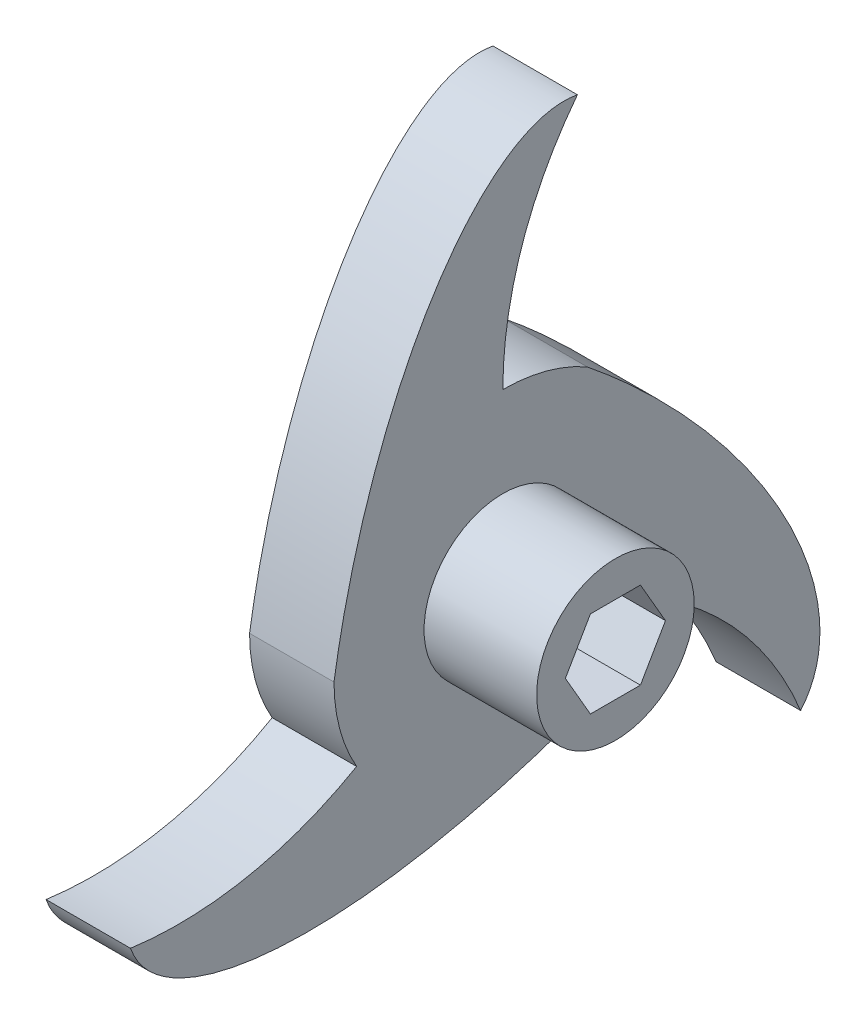
SolidWorks part; units mm, degrees
material "ABS"
ref_plane "Front Plane" through (0, 0, 0) normal (0, 0, 1) x (1, 0, 0)
ref_plane "Top Plane" through (0, 0, 0) normal (0, 1, 0) x (1, 0, 0)
ref_plane "Right Plane" through (0, 0, 0) normal (1, 0, 0) x (0, 0, -1)
sketch "Sketch1" plane through (0, 0, 0) normal (1, 0, 0) x (0, 0, -1)
  line L0 (0, 19.05) -> (101.4565, 19.05) construction
  line L1 (0, 0) -> (0, -44.45) construction
  line L2 (55, 0) -> (-55, 0) construction
  line L3 (0, 0) -> (-44.45, 0) construction
  line L5 (5.6459, 0) -> (2.823, 4.8895)
  line L6 (2.823, 4.8895) -> (-2.823, 4.8895)
  line L7 (-2.823, 4.8895) -> (-5.6459, 0)
  line L8 (-5.6459, 0) -> (-2.823, -4.8895)
  line L9 (-2.823, -4.8895) -> (2.823, -4.8895)
  line L10 (2.823, -4.8895) -> (5.6459, 0)
  circle A0 centre (0, 0) radius 19.05
  circle A1 centre (0, 0) radius 44.45
  arc A2 (0, 19.05) -> (8.4133, 43.6465) centre (40.1609, 19.05) cw
  arc A3 (16.4978, -9.525) -> (33.5923, -29.1094) centre (-3.5827, -44.3054) cw
  arc A4 (-16.4978, -9.525) -> (-42.0056, -14.5371) centre (-36.5782, 25.2554) cw
  circle A5 centre (0, 0) radius 4.8895 construction
  circle A6 centre (0, 0) radius 8.89
  ellipse E0 centre (0, 0) end of major axis (-8.4133, -43.6465) minor radius 18.7675 (8.4133, 43.6465) -> (-19.05, 0) ccw
  ellipse E1 centre (0, 0) end of major axis (33.5923, -29.1094) minor radius 18.7675 (33.5923, -29.1094) -> (9.525, 16.4978) ccw
  ellipse E2 centre (0, 0) end of major axis (-42.0056, -14.5371) minor radius 18.7675 (-42.0056, -14.5371) -> (9.525, -16.4978) ccw
  point P35 (0, 0)
  point P37 (0, 0)
  dimension "D1" = 38.1
  dimension "D2" = 88.9
  dimension "D5" = 9.779
  dimension "D6" = 17.78
  dimension "D3" = 90
  dimension "D7" = 49.3395
  dimension "D4" = 3
extrude "Boss-Extrude2" add sketch "Sketch1" along normal blind 9.525 contours A6 L10 L9 L8 L7 L6 L5 | A0 E2 E1 E0 A6 | A2 E0 A0 | A4 E2 A0 | A3 E1 A0 region at (0, 13.776, -11.9376) region at (0, 27.8134, 4.4553) region at (0, -10.0483, -26.3148) region at (0, -17.7652, 21.8595) region at (0, 0, 8.6386)
extrude "Boss-Extrude4" add sketch "Sketch1<7>" along normal blind 22.225 contours A6 L10 L9 L8 L7 L6 L5 region at (0, 0, 8.6386)
sketch "Sketch1<7>" plane through (0, 0, 0) normal (1, 0, 0) x (0, 0, -1) same geometry as "Sketch1"
